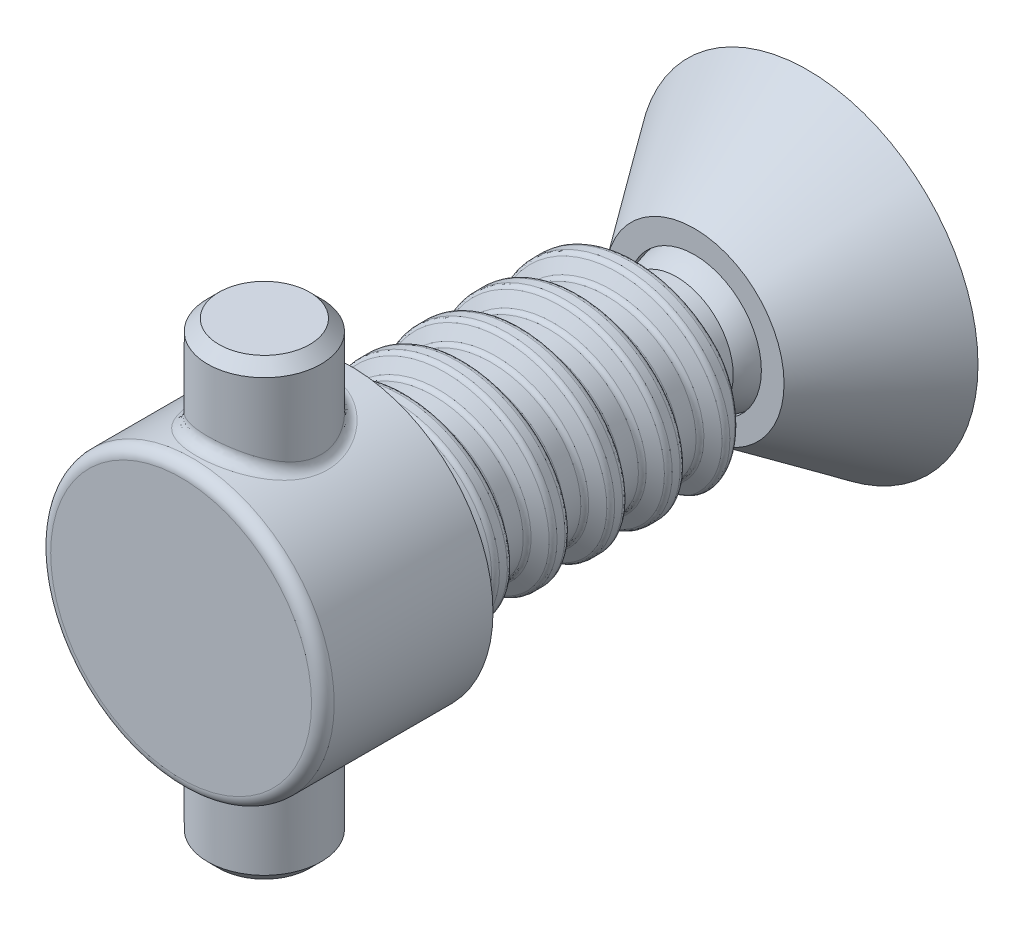
SolidWorks part; units mm, degrees
other "Cap"
ref_plane "Front Plane" through (0, 0, 0) normal (0, 0, 1) x (1, 0, 0)
ref_plane "Top Plane" through (0, 0, 0) normal (0, 1, 0) x (1, 0, 0)
ref_plane "Right Plane" through (0, 0, 0) normal (1, 0, 0) x (0, 0, -1)
sketch "Sketch1" plane through (0, 0, 0) normal (0, 0, 1) x (1, 0, 0)
  circle A0 centre (0, 0) radius 12.5
  dimension "D1" = 25
extrude "Boss-Extrude1" add sketch "Sketch1" along normal blind 15 contours A0
sketch "Sketch2" plane through (0, 0, 0) normal (0, 0, -1) x (-1, 0, 0)
  circle A0 centre (0, 0) radius 7.5
  dimension "D1" = 15
extrude "Boss-Extrude2" add sketch "Sketch2" along normal blind 25
sketch "Sketch3" plane through (0, 0, 0) normal (0, 1, 0) x (1, 0, 0)
  line L0 (0, 0) -> (0, -7.6602) construction
  circle A0 centre (0, -7.6602) radius 5
  dimension "D1" = 10
extrude "Boss-Extrude3" add sketch "Sketch3" along normal blind 20 and the other way blind 20
chamfer "Chamfer1" distance 1 angle 45 2 edges at (0, -20, 12.6602) (0, 20, 12.6602)
fillet "Fillet1" radius 1 3 edges at (12.5, 0, 15) (-0.725, -12.479, 2.713) (0.725, 12.479, 2.713)
thread "Thread1" pitch 5.08 method extrude trim with end face yes profile "Thread Profile2" start angle 0, offset 0, length 0, pitch 5.08, diameter 15
ref_plane "Plane2" through (-7.5, 0, 0) normal (0, -1, 0) x (-1, 0, 0)
sketch "Thread Profile2" plane through (-7.5, 0, 0) normal (0, -1, 0) x (-1, 0, 0)
  line L0 (0, 0) -> (0, 5.08) construction
  line L1 (0, 0) -> (0, 3.6346)
  line L2 (0.508, 3.6346) -> (1.524, 3.6346) construction
  line L3 (1.524, 2.1681) -> (1.524, 1.4665)
  line L4 (1.27, 2.6081) -> (0.254, 3.1946)
  line L5 (1.27, 1.0265) -> (0.254, 0.4399)
  line L6 (0.508, 0) -> (1.524, 0) construction
  arc A0 (0.254, 3.1946) -> (0, 3.6346) centre (0.508, 3.6346) cw
  arc A1 (0.254, 0.4399) -> (0, 0) centre (0.508, 0) ccw
  arc A2 (1.524, 1.4665) -> (1.27, 1.0265) centre (1.016, 1.4665) cw
  arc A3 (1.524, 2.1681) -> (1.27, 2.6081) centre (1.016, 2.1681) ccw
  point P10 (1.524, 2.4614)
  point P17 (1.524, 1.1732)
  point P18 (0, 3.3413)
  point P19 (0, 0.2933)
  point P20 (0, 0)
  dimension "RootFillet1" = 0.508
  dimension "RootFillet2" = 0.508
  dimension "CrestFillet2" = 0.508
  dimension "CrestFillet1" = 0.508
  dimension "Pitch" = 5.08
  dimension "Angle1" = 30
  dimension "Angle2" = 30
  dimension "a" = 3.048
  dimension "b" = 1.524
  dimension "c" = 1.2882
sketch "Sketch5" plane through (0, 0, 0) normal (0, 1, 0) x (1, 0, 0)
  line L0 (-5, 28.6834) -> (-5, 25)
  line L1 (-2.0554, 25) -> (-7.5, 25) construction
  line L2 (-5, 25) -> (5, 25) construction
  line L3 (7.3366, 25) -> (2.0406, 25) construction
  line L4 (5, 25) -> (5, 28.6834) construction
  line L5 (0, 37.6836) -> (0, 27.6836) construction
  line L6 (0, 38) -> (0, 25)
  line L7 (0, 25) -> (-5, 25)
  circle A1 centre (0, 32) radius 6 construction
  arc A2 (-5, 28.6834) -> (0, 38) centre (0, 32) cw
  dimension "D1" = 7
  dimension "D3" = 12
  dimension "D2" = 10
revolve "Revolve3" add sketch "Sketch5" angle 360 about L5
sketch "Sketch7" plane through (0, 0, 0) normal (0, 1, 0) x (1, 0, 0)
  line L4 (0, 0) -> (0, 67.4172) construction
  line L5 (-5.9, 30.2643) -> (5.9, 30.2643) construction
  line L6 (-6, 32) -> (6, 32) construction
  line L7 (-5.9, 30.2643) -> (-7.9, 30.2643) construction
  line L12 (-7.9, 30.2643) -> (-15, 40.2643) construction
  line L13 (-15, 40.2643) -> (15, 40.2643) construction
  line L14 (15, 40.2643) -> (7.9, 30.2643) construction
  line L15 (7.9, 30.2643) -> (5.9, 30.2643) construction
  line L16 (0, 38.15) -> (0, 40.2643)
  line L17 (0, 40.2643) -> (-15, 40.2643)
  line L18 (-15, 40.2643) -> (-7.9, 30.2643)
  line L19 (-7.9, 30.2643) -> (-5.9, 30.2643)
  circle A0 centre (0, 32) radius 6 construction
  arc A1 (5, 28.6834) -> (-5, 28.6834) centre (0, 32) ccw construction
  arc A3 (-5.9, 30.2643) -> (5.9, 30.2643) centre (0, 32) cw construction
  arc A4 (-5.9, 30.2643) -> (0, 38.15) centre (0, 32) cw
  dimension "D4" = 12
  dimension "D5" = 2
  dimension "D1" = 0.15
  dimension "D2" = 0.1
  dimension "D3" = 2
  dimension "D6" = 30
  dimension "D7" = 10
revolve "Revolve4" add sketch "Sketch7" angle 360 about L4
sketch "Sketch8" plane through (0, 0, 0) normal (0, 0, -1) x (-1, 0, 0)
  line L1 (-11, 11) -> (11, 11)
  line L2 (-11, 11) -> (-11, -11)
  line L3 (-11, -11) -> (11, -11)
  line L4 (11, 11) -> (11, -11)
  line L5 (-11, 11) -> (11, -11) construction
  line L6 (-11, -11) -> (11, 11) construction
  point P4 (0, 0)
  dimension "D1" = 22
  dimension "D2" = 22
extrude "Boss-Extrude4" [suppressed] add sketch "Sketch8" along normal blind 16 from offset 3 separate body
other "Intersect1" [suppressed]
combine bodies "Combine1" [suppressed] operation type add bodies to combine 109 110 112
other "Move Face1" [suppressed] flip direction yes offset 0.2 parameters "D1"=0.2
fillet "Fillet2" radius 2 1 edges at (-5, 0, -25)
fillet "Fillet3" radius 0.2 8 edges at (8.6804, -2.4665, -25) (7.9382, 3.9907, -25) (4.4073, 6.8876, -25) (0.4652, 7.5656, -25) (-4.6753, -6.0277, -25) (5.2973, -7.2957, -25) (-0.7255, -8.3476, -25)
